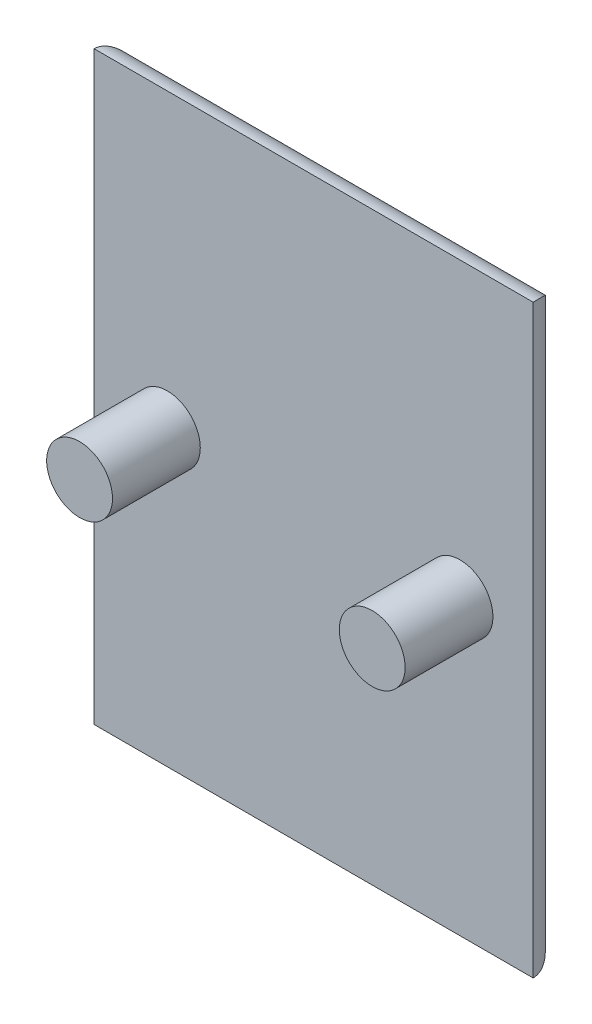
SolidWorks part; units mm, degrees
ref_plane "Front Plane" through (0, 0, 0) normal (0, 0, 1) x (1, 0, 0)
ref_plane "Top Plane" through (0, 0, 0) normal (0, 1, 0) x (1, 0, 0)
ref_plane "Right Plane" through (0, 0, 0) normal (1, 0, 0) x (0, 0, -1)
sketch "Sketch1" plane through (0, 0, 0) normal (0, 0, 1) x (1, 0, 0)
  line L1 (-15, 20) -> (15, 20)
  line L2 (-15, 20) -> (-15, -20)
  line L3 (-15, -20) -> (15, -20)
  line L4 (15, 20) -> (15, -20)
  line L5 (0, -20) -> (0, 20) construction
  line L6 (-15, 0) -> (15, 0) construction
  circle A0 centre (-10, 0) radius 2.25
  circle A1 centre (10, 0) radius 2.25
  point P0 (0, 0)
  dimension "D3" = 5
  dimension "D4" = 4.5
  dimension "D1" = 40
  dimension "D2" = 30
extrude "Boss-Extrude1" add sketch "Sketch1" along normal blind 2
extrude "Boss-Extrude2" add sketch "Sketch1<4>" along normal blind 8 contours A0 | A1 region at (-10, 0, 0) region at (10, 0, 0)
sketch "Sketch1<4>" plane through (0, 0, 0) normal (0, 0, 1) x (1, 0, 0) same geometry as "Sketch1"
fillet "Fillet1" radius 2 4 edges at (0, 20, 0) (-15, 0, 0) (0, -20, 0) (15, 0, 0)
